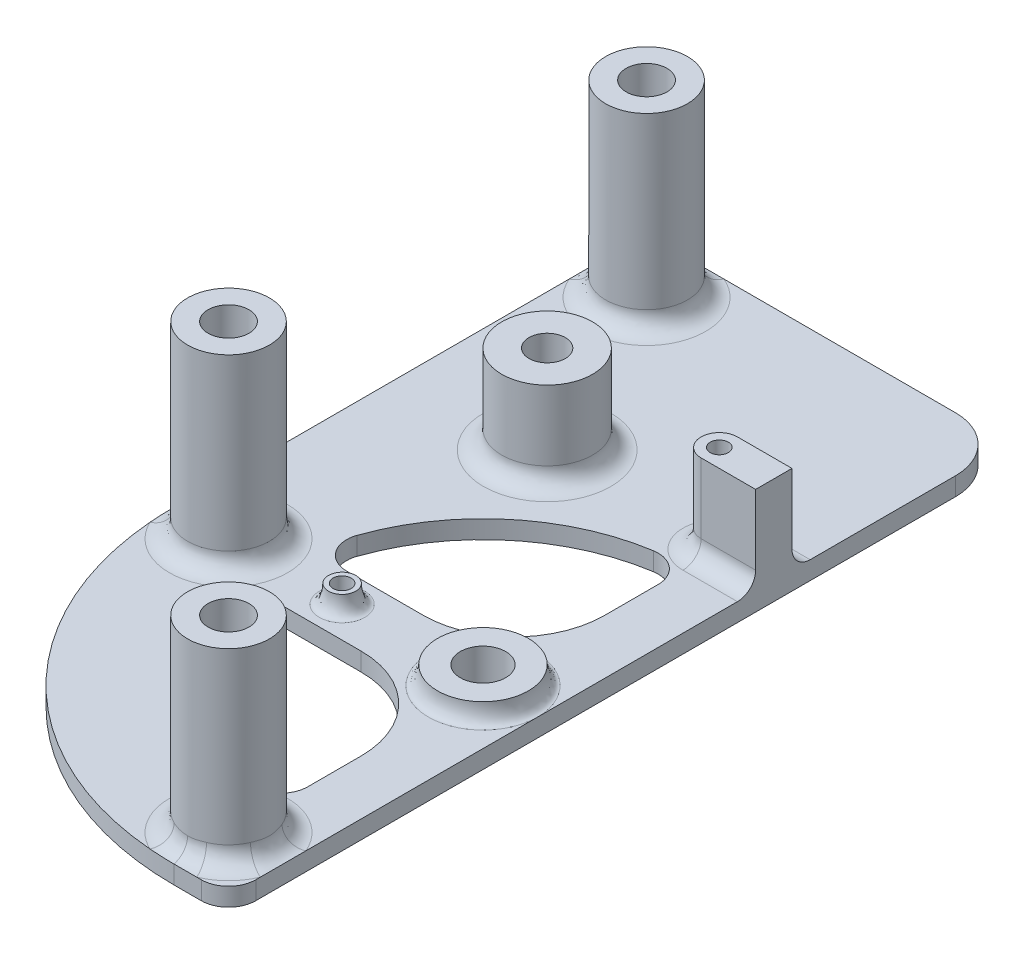
SolidWorks part; units mm, degrees
ref_plane "Plan de face" through (0, 0, 0) normal (0, 0, 1) x (1, 0, 0)
ref_plane "Plan de dessus" through (0, 0, 0) normal (0, 1, 0) x (1, 0, 0)
ref_plane "Plan de droite" through (0, 0, 0) normal (1, 0, 0) x (0, 0, -1)
sketch "Esquisse1" plane through (0, 0, 0) normal (0, 1, 0) x (1, 0, 0)
  line L0 (0, 0) -> (0, 26) construction
  line L1 (0, 0) -> (-15.5, 0) construction
  line L2 (-10, 3.4129) -> (-18.4153, 3.4129)
  line L3 (-34, 0) -> (-34, 46)
  line L4 (-28, 52) -> (0, 52)
  line L5 (0, -34) -> (3, -34)
  line L6 (-28, 0) -> (-28, 81.4672) construction
  line L7 (0, 26) -> (-18.9371, 26) construction
  line L9 (0, 19.2678) -> (0, 13.4129)
  line L11 (6, 46) -> (6, -31)
  line L17 (-10, -3.4129) -> (-18.4153, -3.4129)
  line L18 (0, -13.4129) -> (0, -19.2678)
  circle A0 centre (0, 0) radius 2.5
  circle A1 centre (0, 26) radius 1
  circle A2 centre (-15.5, 0) radius 1
  arc A3 (6, 46) -> (0, 52) centre (0, 46) ccw
  arc A4 (-10, 3.4129) -> (0, 13.4129) centre (-10, 13.4129) ccw
  arc A5 (3, -34) -> (6, -31) centre (3, -31) ccw
  circle A6 centre (-28, 0) radius 2.25
  arc A7 (-10, -3.4129) -> (0, -13.4129) centre (-10, -13.4129) cw
  arc A8 (-34, 46) -> (-28, 52) centre (-28, 46) cw
  circle A9 centre (0, 0) radius 28 construction
  circle A10 centre (0, -28) radius 2.25
  circle A11 centre (-18.9371, 26) radius 2
  arc A12 (-21.2484, -7.3996) -> (-18.4153, -3.4129) centre (-18.4153, -6.4129) cw
  arc A13 (-3.4615, -22.2321) -> (0, -19.2678) centre (-3, -19.2678) ccw
  arc A14 (-3.4615, 22.2321) -> (0, 19.2678) centre (-3, 19.2678) cw
  arc A15 (-21.2484, 7.3996) -> (-18.4153, 3.4129) centre (-18.4153, 6.4129) ccw
  circle A16 centre (-28, 46) radius 2.25
  arc A21 (-3.4615, 22.2321) -> (-21.2484, 7.3996) centre (0, 0) ccw
  arc A22 (-34, 0) -> (0, -34) centre (0, 0) ccw
  arc A23 (-21.2484, -7.3996) -> (-3.4615, -22.2321) centre (0, 0) ccw
  point P25 (0, 23.5)
  point P32 (0, 3.4129)
  point P34 (-10.5, 0)
  point P36 (0, -3.4129)
  point P37 (-5, 0)
  point P40 (0, 5)
  point P43 (0, 21)
  point P44 (0, 22.5)
  point P47 (-2.5, 26)
  point P51 (-13.9371, 26)
  point P55 (-34, 52)
  dimension "D1" = 5
  dimension "D3" = 2
  dimension "D5" = 6
  dimension "D9" = 4.5
  dimension "D10" = 3
  dimension "D7" = 10
  dimension "D11" = 45
  dimension "D12" = 56
  dimension "D6" = 3
  dimension "D13" = 4
  dimension "D14" = 34
  dimension "D16" = 6
  dimension "D2" = 26
  dimension "D4" = 15.5
  dimension "D8" = 18.9371
  dimension "D15" = 52
extrude "Boss.-Extru.1" add sketch "Esquisse1" along normal blind 2
sketch "Esquisse2" plane through (0, 2, 0) normal (0, 1, 0) x (1, 0, 0)
  line L0 (0, 28) -> (6, 28)
  line L3 (0, 24) -> (6, 24)
  line L4 (6, -31) -> (6, 46) construction
  line L5 (6, 24) -> (6, 28)
  circle A0 centre (0, 26) radius 1
  arc A1 (0, 28) -> (0, 24) centre (0, 26) ccw
  circle A2 centre (-18.9371, 26) radius 5
  circle A5 centre (-18.9371, 26) radius 2
  circle A7 centre (-18.9371, 26) radius 2 construction
  dimension "D1" = 4
  dimension "D2" = 10
extrude "Boss.-Extru.2" add sketch "Esquisse2" along normal blind 9.7
sketch "Esquisse3" plane through (0, 2, 0) normal (0, 1, 0) x (1, 0, 0)
  circle A2 centre (0, 0) radius 2.5
  circle A3 centre (0, 0) radius 5
  circle A4 centre (-15.5, 0) radius 1
  circle A5 centre (-15.5, 0) radius 1.5
  dimension "D3" = 10
  dimension "D4" = 3
extrude "Boss.-Extru.3" add sketch "Esquisse3" along normal blind 2
sketch "Esquisse4" plane through (0, 2, 0) normal (0, 1, 0) x (1, 0, 0)
  circle A0 centre (-28, 0) radius 4.5
  circle A1 centre (0, -28) radius 4.5
  circle A2 centre (-28, 0) radius 2.25 construction
  circle A4 centre (-28, 0) radius 2.25
  circle A5 centre (0, -28) radius 2.25
  circle A6 centre (-28, 46) radius 4.5
  circle A7 centre (-28, 46) radius 2.25
  dimension "D1" = 4.5
extrude "Boss.-Extru.4" add sketch "Esquisse4" along normal blind 20.7
fillet "Congé2" radius 1 2 edges at (0, 2, 5) (-15.5, 2, 1.5) second distance 2 first distance on face at (0, 2, 32.5)
fillet "Congé3" radius 2 7 edges at (-2, 2, -26) (3, 2, -24) (-28, 2, 4.5) (0, 2, 32.5) (3, 2, -28) (-18.9371, 2, -21) (-28, 2, -41.5)
